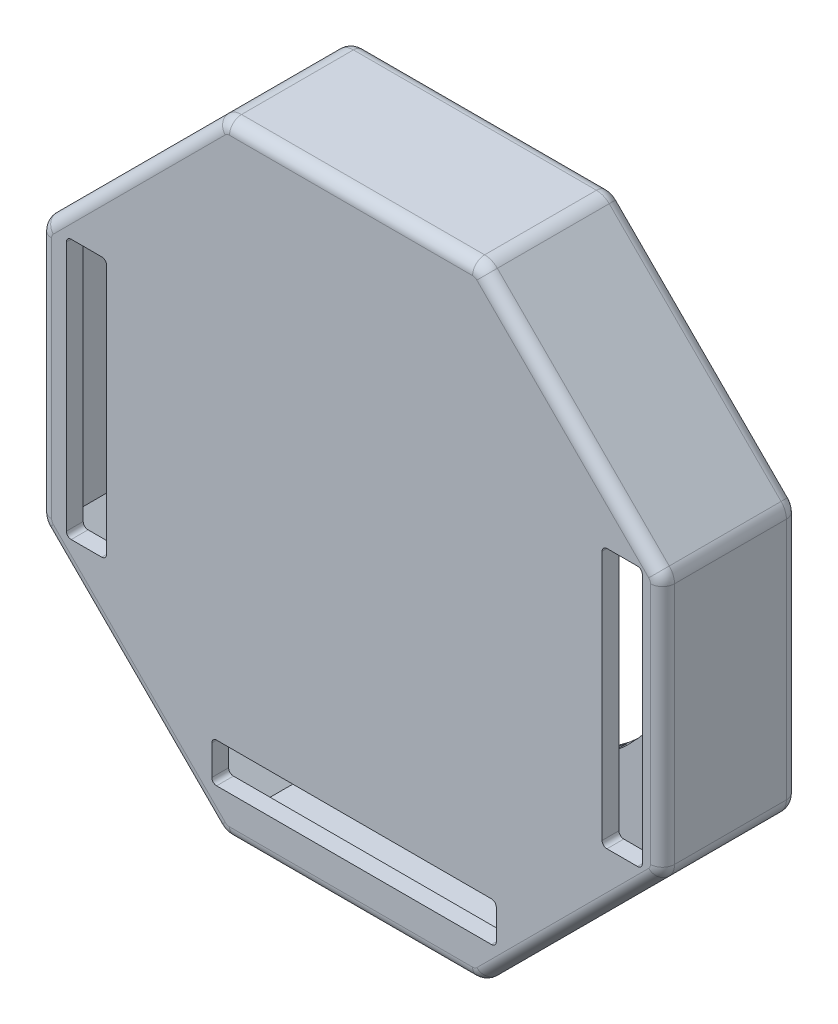
SolidWorks part; units mm, degrees
note: The reader was unsure of these and kept them because the rebuilt part matched: shared geometry of "Sketch9<3>".
ref_plane "Front Plane" through (0, 0, 0) normal (0, 0, 1) x (1, 0, 0)
ref_plane "Top Plane" through (0, 0, 0) normal (0, 1, 0) x (1, 0, 0)
ref_plane "Right Plane" through (0, 0, 0) normal (1, 0, 0) x (0, 0, -1)
sketch "Sketch1" plane through (0, 0, 0) normal (0, 0, 1) x (1, 0, 0)
  line L0 (25.9, -10.1068) -> (25.9, 10.1068) construction
  line L1 (25.4607, 11.1675) -> (22.5059, 14.1222) construction
  line L2 (22.5059, 14.1222) -> (21.5159, 13.1323) construction
  line L3 (21.5159, 13.1323) -> (24.5, 10.1482) construction
  line L4 (24.5, 10.1482) -> (24.5, -10.1482) construction
  line L5 (24.5, -10.1482) -> (21.6927, -12.9555) construction
  line L6 (21.6927, -12.9555) -> (22.6827, -13.9455) construction
  line L7 (22.6827, -13.9455) -> (25.4607, -11.1675) construction
  line L8 (-16.1773, -20.4508) -> (-11.1675, -25.4607) construction
  line L9 (-10.1068, -25.9) -> (10.1068, -25.9) construction
  line L10 (11.1675, -25.4607) -> (15.6116, -21.0165) construction
  line L11 (15.6116, -21.0165) -> (14.6216, -20.0266) construction
  line L12 (14.6216, -20.0266) -> (10.1482, -24.5) construction
  line L13 (10.1482, -24.5) -> (-10.1482, -24.5) construction
  line L14 (-10.1482, -24.5) -> (-15.1873, -19.4609) construction
  line L15 (-15.1873, -19.4609) -> (-16.1773, -20.4508) construction
  line L16 (-22.117, 14.5112) -> (-25.4607, 11.1675) construction
  line L17 (-25.9, 10.1068) -> (-25.9, -10.1068) construction
  line L18 (-25.4607, -11.1675) -> (-22.1877, -14.4404) construction
  line L19 (-22.1877, -14.4404) -> (-21.1977, -13.4505) construction
  line L20 (-21.1977, -13.4505) -> (-24.5, -10.1482) construction
  line L21 (-24.5, -10.1482) -> (-24.5, 10.1482) construction
  line L22 (-24.5, 10.1482) -> (-21.127, 13.5212) construction
  line L23 (-21.127, 13.5212) -> (-22.117, 14.5112) construction
  line L24 (10.1068, 25.9) -> (-10.1068, 25.9) construction
  line L25 (-11.1675, 25.4607) -> (-17.5208, 19.1073) construction
  line L26 (-17.5208, 19.1073) -> (-16.5308, 18.1174) construction
  line L27 (-16.5308, 18.1174) -> (-10.1482, 24.5) construction
  line L28 (-10.1482, 24.5) -> (10.1482, 24.5) construction
  line L29 (10.1482, 24.5) -> (16.9197, 17.7285) construction
  line L30 (16.9197, 17.7285) -> (17.9097, 18.7184) construction
  line L32 (25.9, -10.1068) -> (25.9, 10.1068)
  line L33 (25.4607, 11.1675) -> (22.5059, 14.1222)
  line L34 (22.5059, 14.1222) -> (21.5159, 13.1323)
  line L35 (21.5159, 13.1323) -> (24.5, 10.1482)
  line L36 (24.5, 10.1482) -> (24.5, -10.1482)
  line L37 (24.5, -10.1482) -> (21.6927, -12.9555)
  line L38 (21.6927, -12.9555) -> (22.6827, -13.9455)
  line L39 (22.6827, -13.9455) -> (25.4607, -11.1675)
  line L40 (-16.1773, -20.4508) -> (-11.1675, -25.4607)
  line L41 (-10.1068, -25.9) -> (10.1068, -25.9)
  line L42 (11.1675, -25.4607) -> (15.6116, -21.0165)
  line L43 (15.6116, -21.0165) -> (14.6216, -20.0266)
  line L44 (14.6216, -20.0266) -> (10.1482, -24.5)
  line L45 (10.1482, -24.5) -> (-10.1482, -24.5)
  line L46 (-10.1482, -24.5) -> (-15.1873, -19.4609)
  line L47 (-15.1873, -19.4609) -> (-16.1773, -20.4508)
  line L48 (-22.117, 14.5112) -> (-25.4607, 11.1675)
  line L49 (-25.9, 10.1068) -> (-25.9, -10.1068)
  line L50 (-25.4607, -11.1675) -> (-22.1877, -14.4404)
  line L51 (-22.1877, -14.4404) -> (-21.1977, -13.4505)
  line L52 (-21.1977, -13.4505) -> (-24.5, -10.1482)
  line L53 (-24.5, -10.1482) -> (-24.5, 10.1482)
  line L54 (-24.5, 10.1482) -> (-21.127, 13.5212)
  line L55 (-21.127, 13.5212) -> (-22.117, 14.5112)
  line L56 (10.1068, 25.9) -> (-10.1068, 25.9)
  line L57 (-11.1675, 25.4607) -> (-17.5208, 19.1073)
  line L58 (-17.5208, 19.1073) -> (-16.5308, 18.1174)
  line L59 (-16.5308, 18.1174) -> (-10.1482, 24.5)
  line L60 (-10.1482, 24.5) -> (10.1482, 24.5)
  line L61 (10.1482, 24.5) -> (16.9197, 17.7285)
  line L62 (16.9197, 17.7285) -> (17.9097, 18.7184)
  line L64 (17.9097, 18.7184) -> (11.1675, 25.4607)
  line L66 (-17.5208, 19.1073) -> (-16.5308, 18.1174)
  line L67 (-21.127, 13.5212) -> (-22.117, 14.5112)
  arc A0 (25.9, 10.1068) -> (25.4607, 11.1675) centre (24.4, 10.1068) ccw construction
  arc A1 (25.4607, -11.1675) -> (25.9, -10.1068) centre (24.4, -10.1068) ccw construction
  arc A2 (-11.1675, -25.4607) -> (-10.1068, -25.9) centre (-10.1068, -24.4) ccw construction
  arc A3 (10.1068, -25.9) -> (11.1675, -25.4607) centre (10.1068, -24.4) ccw construction
  arc A4 (-25.4607, 11.1675) -> (-25.9, 10.1068) centre (-24.4, 10.1068) ccw construction
  arc A5 (-25.9, -10.1068) -> (-25.4607, -11.1675) centre (-24.4, -10.1068) ccw construction
  arc A6 (-10.1068, 25.9) -> (-11.1675, 25.4607) centre (-10.1068, 24.4) ccw construction
  arc A7 (11.1675, 25.4607) -> (10.1068, 25.9) centre (10.1068, 24.4) ccw construction
  arc A8 (25.9, 10.1068) -> (25.4607, 11.1675) centre (24.4, 10.1068) ccw
  arc A9 (25.4607, -11.1675) -> (25.9, -10.1068) centre (24.4, -10.1068) ccw
  arc A10 (-11.1675, -25.4607) -> (-10.1068, -25.9) centre (-10.1068, -24.4) ccw
  arc A11 (10.1068, -25.9) -> (11.1675, -25.4607) centre (10.1068, -24.4) ccw
  arc A12 (-25.4607, 11.1675) -> (-25.9, 10.1068) centre (-24.4, 10.1068) ccw
  arc A13 (-25.9, -10.1068) -> (-25.4607, -11.1675) centre (-24.4, -10.1068) ccw
  arc A14 (-10.1068, 25.9) -> (-11.1675, 25.4607) centre (-10.1068, 24.4) ccw
  arc A15 (11.1675, 25.4607) -> (10.1068, 25.9) centre (10.1068, 24.4) ccw
extrude "Boss-Extrude1" add sketch "Sketch1" along normal blind 8.5
sketch "Sketch2" plane through (0, 0, 8.5) normal (0, 0, 1) x (1, 0, 0)
  line L0 (22.6827, -13.9455) -> (25.4607, -11.1675) construction
  line L1 (25.9, -10.1068) -> (25.9, 10.1068) construction
  line L2 (25.4607, 11.1675) -> (22.5059, 14.1222) construction
  line L3 (22.5059, 14.1222) -> (21.5159, 13.1323) construction
  line L4 (21.5159, 13.1323) -> (24.5, 10.1482) construction
  line L5 (24.5, 10.1482) -> (24.5, -10.1482) construction
  line L6 (24.5, -10.1482) -> (21.6927, -12.9555) construction
  line L7 (21.6927, -12.9555) -> (22.6827, -13.9455) construction
  line L8 (-10.1068, -25.9) -> (10.1068, -25.9) construction
  line L9 (11.1675, -25.4607) -> (15.6116, -21.0165) construction
  line L10 (15.6116, -21.0165) -> (14.6216, -20.0266) construction
  line L11 (14.6216, -20.0266) -> (10.1482, -24.5) construction
  line L12 (10.1482, -24.5) -> (-10.1482, -24.5) construction
  line L13 (-10.1482, -24.5) -> (-15.1873, -19.4609) construction
  line L14 (-15.1873, -19.4609) -> (-16.1773, -20.4508) construction
  line L15 (-16.1773, -20.4508) -> (-11.1675, -25.4607) construction
  line L16 (-25.9, 10.1068) -> (-25.9, -10.1068) construction
  line L17 (-25.4607, -11.1675) -> (-22.1877, -14.4404) construction
  line L18 (-22.1877, -14.4404) -> (-21.1977, -13.4505) construction
  line L19 (-21.1977, -13.4505) -> (-24.5, -10.1482) construction
  line L20 (-24.5, -10.1482) -> (-24.5, 10.1482) construction
  line L21 (-24.5, 10.1482) -> (-21.127, 13.5212) construction
  line L22 (-21.127, 13.5212) -> (-22.117, 14.5112) construction
  line L23 (-22.117, 14.5112) -> (-25.4607, 11.1675) construction
  line L24 (17.9097, 18.7184) -> (11.1675, 25.4607) construction
  line L25 (10.1068, 25.9) -> (-10.1068, 25.9) construction
  line L26 (-11.1675, 25.4607) -> (-17.5208, 19.1073) construction
  line L27 (-17.5208, 19.1073) -> (-16.5308, 18.1174) construction
  line L28 (-16.5308, 18.1174) -> (-10.1482, 24.5) construction
  line L29 (-10.1482, 24.5) -> (10.1482, 24.5) construction
  line L30 (10.1482, 24.5) -> (16.9197, 17.7285) construction
  line L31 (16.9197, 17.7285) -> (17.9097, 18.7184) construction
  line L32 (22.6827, -13.9455) -> (25.4607, -11.1675)
  line L33 (25.9, -10.1068) -> (25.9, 10.1068)
  line L34 (25.4607, 11.1675) -> (22.5059, 14.1222)
  line L35 (22.5059, 14.1222) -> (21.5159, 13.1323)
  line L36 (21.5159, 13.1323) -> (24.5, 10.1482)
  line L37 (24.5, 10.1482) -> (24.5, -10.1482)
  line L38 (24.5, -10.1482) -> (21.6927, -12.9555)
  line L39 (21.6927, -12.9555) -> (22.6827, -13.9455)
  line L40 (-10.1068, -25.9) -> (10.1068, -25.9)
  line L41 (11.1675, -25.4607) -> (15.6116, -21.0165)
  line L42 (15.6116, -21.0165) -> (14.6216, -20.0266)
  line L43 (14.6216, -20.0266) -> (10.1482, -24.5)
  line L44 (10.1482, -24.5) -> (-10.1482, -24.5)
  line L45 (-10.1482, -24.5) -> (-15.1873, -19.4609)
  line L46 (-15.1873, -19.4609) -> (-16.1773, -20.4508)
  line L47 (-16.1773, -20.4508) -> (-11.1675, -25.4607)
  line L48 (-25.9, 10.1068) -> (-25.9, -10.1068)
  line L49 (-25.4607, -11.1675) -> (-22.1877, -14.4404)
  line L50 (-22.1877, -14.4404) -> (-21.1977, -13.4505)
  line L51 (-21.1977, -13.4505) -> (-24.5, -10.1482)
  line L52 (-24.5, -10.1482) -> (-24.5, 10.1482)
  line L53 (-24.5, 10.1482) -> (-21.127, 13.5212)
  line L54 (-21.127, 13.5212) -> (-22.117, 14.5112)
  line L55 (-22.117, 14.5112) -> (-25.4607, 11.1675)
  line L56 (17.9097, 18.7184) -> (11.1675, 25.4607)
  line L57 (10.1068, 25.9) -> (-10.1068, 25.9)
  line L58 (-11.1675, 25.4607) -> (-17.5208, 19.1073)
  line L59 (-17.5208, 19.1073) -> (-16.5308, 18.1174)
  line L60 (-16.5308, 18.1174) -> (-10.1482, 24.5)
  line L61 (-10.1482, 24.5) -> (10.1482, 24.5)
  line L62 (10.1482, 24.5) -> (16.9197, 17.7285)
  line L63 (16.9197, 17.7285) -> (17.9097, 18.7184)
  line L64 (-22.117, 14.5112) -> (-17.5208, 19.1073)
  line L65 (-16.5308, 18.1174) -> (-21.127, 13.5212)
  line L66 (-21.1977, -13.4505) -> (-15.1873, -19.4609)
  line L67 (-16.1773, -20.4508) -> (-22.1877, -14.4404)
  line L68 (14.6216, -20.0266) -> (21.6927, -12.9555)
  line L69 (22.6827, -13.9455) -> (15.6116, -21.0165)
  line L70 (22.5059, 14.1222) -> (17.9097, 18.7184)
  line L71 (21.5159, 13.1323) -> (16.9197, 17.7285)
  arc A0 (25.4607, -11.1675) -> (25.9, -10.1068) centre (24.4, -10.1068) ccw construction
  arc A1 (25.9, 10.1068) -> (25.4607, 11.1675) centre (24.4, 10.1068) ccw construction
  arc A2 (10.1068, -25.9) -> (11.1675, -25.4607) centre (10.1068, -24.4) ccw construction
  arc A3 (-11.1675, -25.4607) -> (-10.1068, -25.9) centre (-10.1068, -24.4) ccw construction
  arc A4 (-25.9, -10.1068) -> (-25.4607, -11.1675) centre (-24.4, -10.1068) ccw construction
  arc A5 (-25.4607, 11.1675) -> (-25.9, 10.1068) centre (-24.4, 10.1068) ccw construction
  arc A6 (11.1675, 25.4607) -> (10.1068, 25.9) centre (10.1068, 24.4) ccw construction
  arc A7 (-10.1068, 25.9) -> (-11.1675, 25.4607) centre (-10.1068, 24.4) ccw construction
  arc A8 (25.4607, -11.1675) -> (25.9, -10.1068) centre (24.4, -10.1068) ccw
  arc A9 (25.9, 10.1068) -> (25.4607, 11.1675) centre (24.4, 10.1068) ccw
  arc A10 (10.1068, -25.9) -> (11.1675, -25.4607) centre (10.1068, -24.4) ccw
  arc A11 (-11.1675, -25.4607) -> (-10.1068, -25.9) centre (-10.1068, -24.4) ccw
  arc A12 (-25.9, -10.1068) -> (-25.4607, -11.1675) centre (-24.4, -10.1068) ccw
  arc A13 (-25.4607, 11.1675) -> (-25.9, 10.1068) centre (-24.4, 10.1068) ccw
  arc A14 (11.1675, 25.4607) -> (10.1068, 25.9) centre (10.1068, 24.4) ccw
  arc A15 (-10.1068, 25.9) -> (-11.1675, 25.4607) centre (-10.1068, 24.4) ccw
extrude "Boss-Extrude2" add sketch "Sketch2" along normal blind 1.4
sketch "Sketch3" plane through (0, 0, 8.5) normal (0, 0, -1) x (-1, 0, 0)
  line L0 (-21.5159, 13.1323) -> (-16.9197, 17.7285)
  line L1 (-16.9197, 17.7285) -> (-17.9097, 18.7184)
  line L2 (-17.9097, 18.7184) -> (-22.5059, 14.1222)
  line L3 (-22.5059, 14.1222) -> (-21.5159, 13.1323)
  line L4 (21.127, 13.5212) -> (16.5308, 18.1174)
  line L5 (16.5308, 18.1174) -> (17.5208, 19.1073)
  line L6 (17.5208, 19.1073) -> (22.117, 14.5112)
  line L7 (22.117, 14.5112) -> (21.127, 13.5212)
  line L8 (-21.6927, -12.9555) -> (-22.6827, -13.9455)
  line L9 (-21.6927, -12.9555) -> (-22.6827, -13.9455) construction
  line L10 (-22.6827, -13.9455) -> (-15.6116, -21.0165)
  line L11 (-15.6116, -21.0165) -> (-14.6216, -20.0266)
  line L12 (-14.6216, -20.0266) -> (-21.6927, -12.9555)
  line L13 (15.1873, -19.4609) -> (16.1773, -20.4508)
  line L14 (16.1773, -20.4508) -> (22.1877, -14.4404)
  line L15 (22.1877, -14.4404) -> (21.1977, -13.4505)
  line L16 (21.1977, -13.4505) -> (15.1873, -19.4609)
extrude "Boss-Extrude3" add sketch "Sketch3" along normal blind 8.5 contours L7 L4 L5 L6 | L3 L0 L1 L2 | L16 L13 L14 L15 | L12 L8 L10 L11
sketch "Sketch5" plane through (0, 0, 8.5) normal (0, 0, -1) x (-1, 0, 0)
  line L0 (16.1773, -20.4508) -> (22.1877, -14.4404)
  line L1 (22.1877, -14.4404) -> (21.1977, -13.4505)
  line L2 (21.1977, -13.4505) -> (15.1873, -19.4609)
  line L3 (15.1873, -19.4609) -> (16.1773, -20.4508)
extrude "Boss-Extrude5" add sketch "Sketch5" along normal blind 1
sketch "Sketch6" plane through (0, 0, 9.9) normal (0, 0, 1) x (1, 0, 0)
  line L0 (-23.2729, -10.394) -> (-20.7329, -10.394) construction
  line L1 (-23.2729, 10.434) -> (-23.2729, -10.394) construction
  line L2 (-20.7329, -10.394) -> (-20.7329, 10.434) construction
  line L3 (-20.7329, 10.434) -> (-23.2729, 10.434) construction
  line L4 (21.2779, -10.389) -> (23.8179, -10.389) construction
  line L5 (23.8179, -10.389) -> (23.8179, 10.439) construction
  line L6 (21.2779, 10.439) -> (21.2779, -10.389) construction
  line L7 (23.8179, 10.439) -> (21.2779, 10.439) construction
  line L8 (-23.2729, -10.394) -> (-20.7329, -10.394)
  line L9 (-23.2729, 10.434) -> (-23.2729, -10.394)
  line L10 (-20.7329, -10.394) -> (-20.7329, 10.434)
  line L11 (-20.7329, 10.434) -> (-23.2729, 10.434)
  line L12 (21.2779, -10.389) -> (23.8179, -10.389)
  line L13 (23.8179, -10.389) -> (23.8179, 10.439)
  line L14 (21.2779, 10.439) -> (21.2779, -10.389)
  line L15 (23.8179, 10.439) -> (21.2779, 10.439)
  line L16 (-20.3329, -10.394) -> (-20.3329, 10.434)
  line L17 (-20.7329, 10.834) -> (-23.2729, 10.834)
  line L18 (-23.6729, 10.434) -> (-23.6729, -10.394)
  line L19 (-23.2729, -10.794) -> (-20.7329, -10.794)
  line L20 (21.2779, -10.789) -> (23.8179, -10.789)
  line L21 (24.2179, -10.389) -> (24.2179, 10.439)
  line L22 (23.8179, 10.839) -> (21.2779, 10.839)
  line L23 (20.8779, 10.439) -> (20.8779, -10.389)
  line L24 (24.2179, 10.839) -> (20.8779, 10.839) construction
  line L25 (20.8779, 10.839) -> (20.8779, -10.789) construction
  line L26 (24.2179, -10.789) -> (24.2179, 10.839) construction
  line L27 (20.8779, -10.789) -> (24.2179, -10.789) construction
  line L28 (-20.3329, -10.794) -> (-20.3329, 10.834) construction
  line L29 (-23.6729, -10.794) -> (-20.3329, -10.794) construction
  line L30 (-23.6729, 10.834) -> (-23.6729, -10.794) construction
  line L31 (-20.3329, 10.834) -> (-23.6729, 10.834) construction
  arc A0 (21.2779, 10.839) -> (20.8779, 10.439) centre (21.2779, 10.439) ccw
  arc A1 (24.2179, 10.439) -> (23.8179, 10.839) centre (23.8179, 10.439) ccw
  arc A2 (23.8179, -10.789) -> (24.2179, -10.389) centre (23.8179, -10.389) ccw
  arc A3 (21.2779, -10.789) -> (20.8779, -10.389) centre (21.2779, -10.389) cw
  arc A4 (-20.3329, -10.394) -> (-20.7329, -10.794) centre (-20.7329, -10.394) cw
  arc A5 (-23.6729, -10.394) -> (-23.2729, -10.794) centre (-23.2729, -10.394) ccw
  arc A6 (-20.3329, 10.434) -> (-20.7329, 10.834) centre (-20.7329, 10.434) ccw
  arc A7 (-23.2729, 10.834) -> (-23.6729, 10.434) centre (-23.2729, 10.434) ccw
  dimension "D2" = 0.4
  dimension "D1" = 0.4
extrude "Cut-Extrude1" cut sketch "Sketch6" against normal through all
sketch "Sketch7" plane through (0, 0, 9.9) normal (0, 0, 1) x (1, 0, 0)
  line L0 (9.3915, -22.0846) -> (11.6775, -22.0846) construction
  line L1 (11.6775, -22.0846) -> (11.6775, -19.5954) construction
  line L2 (-11.1825, -22.0846) -> (-8.8965, -22.0846) construction
  line L3 (-11.1825, -19.5954) -> (-11.1825, -22.0846) construction
  line L4 (9.3915, -22.0846) -> (11.6775, -22.0846)
  line L5 (11.6775, -22.0846) -> (11.6775, -19.5954)
  line L6 (-11.1825, -22.0846) -> (-8.8965, -22.0846)
  line L7 (-11.1825, -19.5954) -> (-11.1825, -22.0846)
  line L8 (-11.1825, -19.5954) -> (11.6775, -19.5954)
  line L9 (9.3915, -22.0846) -> (-8.8965, -22.0846)
  line L10 (9.3915, -22.4846) -> (-8.8965, -22.4846)
  line L11 (-11.1825, -22.4846) -> (-8.8965, -22.4846)
  line L12 (-11.5825, -19.5954) -> (-11.5825, -22.0846)
  line L13 (-11.1825, -19.1954) -> (11.6775, -19.1954)
  line L14 (12.0775, -22.0846) -> (12.0775, -19.5954)
  line L15 (9.3915, -22.4846) -> (11.6775, -22.4846)
  line L16 (-11.5825, -19.1954) -> (12.0775, -19.1954) construction
  line L17 (12.0775, -22.4846) -> (12.0775, -19.1954) construction
  line L18 (9.3915, -22.4846) -> (12.0775, -22.4846) construction
  line L19 (-11.5825, -22.4846) -> (-8.8965, -22.4846) construction
  line L20 (-11.5825, -19.1954) -> (-11.5825, -22.4846) construction
  arc A0 (11.6775, -19.1954) -> (12.0775, -19.5954) centre (11.6775, -19.5954) cw
  arc A1 (12.0775, -22.0846) -> (11.6775, -22.4846) centre (11.6775, -22.0846) cw
  arc A2 (-11.1825, -22.4846) -> (-11.5825, -22.0846) centre (-11.1825, -22.0846) cw
  arc A3 (-11.5825, -19.5954) -> (-11.1825, -19.1954) centre (-11.1825, -19.5954) cw
  dimension "D2" = 0.4
  dimension "D1" = 0.4
extrude "Cut-Extrude2" cut sketch "Sketch7" against normal through all contours L9 L4 L5 L8 L7 L6 | A3 L12 A2 L11 L10 L15 A1 L14 A0 L13 L4 L9 L6 L7 L8 L5
fillet "Fillet1" radius 1 16 edges at (10.6808, -25.7858, 9.9) (0, -25.9, 9.9) (-10.6808, -25.7858, 9.9) (-18.3141, -18.3141, 9.9) (-25.7858, -10.6808, 9.9) (-25.9, 0, 9.9) (-25.7858, 10.6808, 9.9) (-18.3141, 18.3141, 9.9) (-10.6808, 25.7858, 9.9) (0, 25.9, 9.9) (10.6808, 25.7858, 9.9) (18.3141, 18.3141, 9.9) (25.7858, 10.6808, 9.9) (25.9, 0, 9.9) (25.7858, -10.6808, 9.9) (18.3141, -18.3141, 9.9)
sketch "Sketch8" plane through (0, 0, 0) normal (0, 0, -1) x (-1, 0, 0)
  line L8 (-11.1675, 25.4607) -> (-25.4607, 11.1675)
  line L9 (-25.9, 10.1068) -> (-25.9, -10.1068)
  line L10 (-25.4607, -11.1675) -> (-11.1675, -25.4607)
  line L11 (-10.1068, -25.9) -> (10.1068, -25.9)
  line L12 (11.1675, -25.4607) -> (25.4607, -11.1675)
  line L13 (25.9, -10.1068) -> (25.9, 10.1068)
  line L14 (25.4607, 11.1675) -> (11.1675, 25.4607)
  line L15 (10.1068, 25.9) -> (-10.1068, 25.9)
  line L16 (-11.1675, 25.4607) -> (-25.4607, 11.1675)
  line L17 (-25.9, 10.1068) -> (-25.9, -10.1068)
  line L18 (-25.4607, -11.1675) -> (-11.1675, -25.4607)
  line L19 (-10.1068, -25.9) -> (10.1068, -25.9)
  line L20 (11.1675, -25.4607) -> (25.4607, -11.1675)
  line L21 (25.9, -10.1068) -> (25.9, 10.1068)
  line L22 (25.4607, 11.1675) -> (11.1675, 25.4607)
  line L23 (10.1068, 25.9) -> (-10.1068, 25.9)
  arc A8 (-25.4607, 11.1675) -> (-25.9, 10.1068) centre (-24.4, 10.1068) ccw
  arc A9 (-25.9, -10.1068) -> (-25.4607, -11.1675) centre (-24.4, -10.1068) ccw
  arc A10 (-11.1675, -25.4607) -> (-10.1068, -25.9) centre (-10.1068, -24.4) ccw
  arc A11 (10.1068, -25.9) -> (11.1675, -25.4607) centre (10.1068, -24.4) ccw
  arc A12 (25.4607, -11.1675) -> (25.9, -10.1068) centre (24.4, -10.1068) ccw
  arc A13 (25.9, 10.1068) -> (25.4607, 11.1675) centre (24.4, 10.1068) ccw
  arc A14 (11.1675, 25.4607) -> (10.1068, 25.9) centre (10.1068, 24.4) ccw
  arc A15 (-10.1068, 25.9) -> (-11.1675, 25.4607) centre (-10.1068, 24.4) ccw
  arc A16 (-25.4607, 11.1675) -> (-25.9, 10.1068) centre (-24.4, 10.1068) ccw
  arc A17 (-25.9, -10.1068) -> (-25.4607, -11.1675) centre (-24.4, -10.1068) ccw
  arc A18 (-11.1675, -25.4607) -> (-10.1068, -25.9) centre (-10.1068, -24.4) ccw
  arc A19 (10.1068, -25.9) -> (11.1675, -25.4607) centre (10.1068, -24.4) ccw
  arc A20 (25.4607, -11.1675) -> (25.9, -10.1068) centre (24.4, -10.1068) ccw
  arc A21 (25.9, 10.1068) -> (25.4607, 11.1675) centre (24.4, 10.1068) ccw
  arc A22 (11.1675, 25.4607) -> (10.1068, 25.9) centre (10.1068, 24.4) ccw
  arc A23 (-10.1068, 25.9) -> (-11.1675, 25.4607) centre (-10.1068, 24.4) ccw
  dimension "D1" = 0
extrude "Boss-Extrude6" add sketch "Sketch8" along normal blind 1.4
fillet "Fillet2" radius 1 16 edges at (0, 25.9, -1.4) (-10.6808, 25.7858, -1.4) (-18.3141, 18.3141, -1.4) (-25.7858, 10.6808, -1.4) (-25.9, 0, -1.4) (-25.7858, -10.6808, -1.4) (-18.3141, -18.3141, -1.4) (-10.6808, -25.7858, -1.4) (0, -25.9, -1.4) (10.6808, -25.7858, -1.4) (18.3141, -18.3141, -1.4) (25.7858, -10.6808, -1.4) (25.9, 0, -1.4) (25.7858, 10.6808, -1.4) (18.3141, 18.3141, -1.4) (10.6808, 25.7858, -1.4)
sketch "Sketch9" plane through (0, 0, -1.4) normal (0, 0, -1) x (-1, 0, 0)
  line L0 (-18.5, 0.5) -> (17.5, 0.5) construction
  line L1 (25.9, 10.1068) -> (25.9, -10.1068) construction
  line L3 (-0.5, -17.5) -> (-0.5, 18.5) construction
  line L4 (10.1068, -25.9) -> (-10.1068, -25.9) construction
  line L5 (-9.5, -15.0885) -> (8.5, -15.0885)
  line L6 (-8, -21.5885) -> (7, -21.5885)
  line L7 (-9.5, -15.0885) -> (-8, -21.5885)
  line L8 (7, -21.5885) -> (8.5, -15.0885)
  circle A1 centre (-0.5, 0.5) radius 18
  point P4 (-0.5, 0.5)
  point P9 (-0.5, 0.5)
  point P17 (-0.5, -21.5885)
  dimension "D1" = 36
  dimension "D2" = 44.4
  dimension "D3" = 44.4
  dimension "D4" = 18
  dimension "D5" = 15
  dimension "D6" = 6.5
extrude "Cut-Extrude3" cut sketch "Sketch9" against normal blind 1.4 contours L5 A1 | L5 A1 | A1 L7 L6 L8
extrude "Boss-Extrude7" add sketch "Sketch9<3>" against normal blind 0.25 contours A1 L7 L6 L8
sketch "Sketch9<3>" plane through (0, 0, -1.4) normal (0, 0, -1) x (-1, 0, 0) same geometry as "Sketch9"
fillet "Fillet3" radius 10 2 edges at (9.5, -15.0885, -0.575) (-8.5, -15.0885, -0.575)
